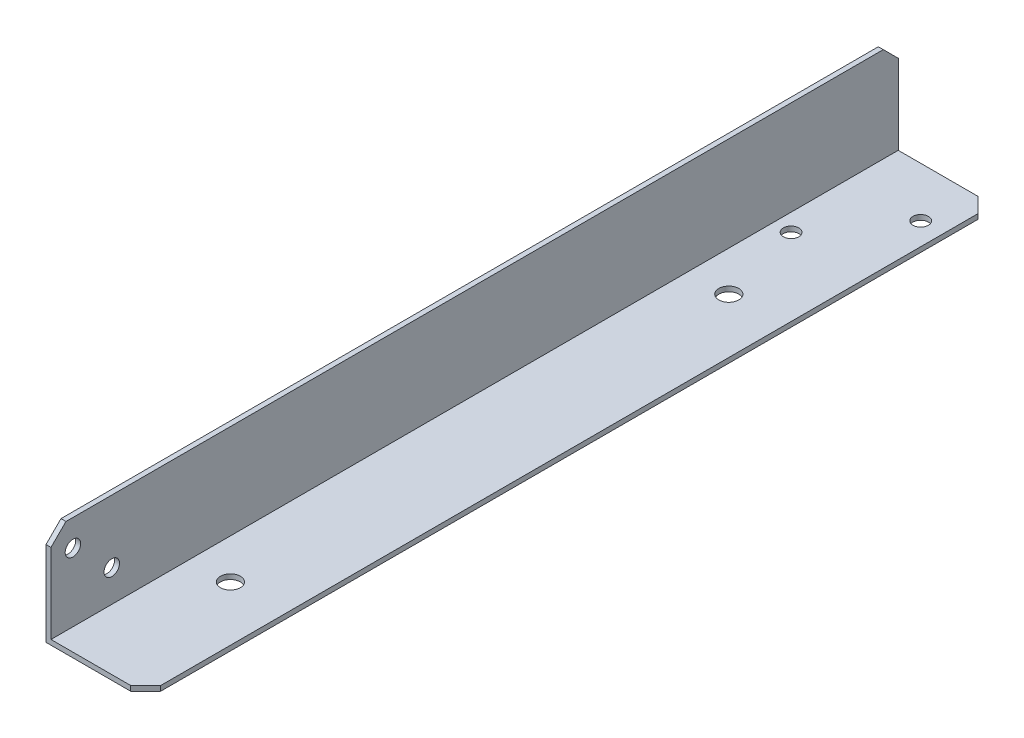
SolidWorks part; units mm, degrees
material "6063-T5"
ref_plane "Спереди" through (0, 0, 0) normal (0, 0, 1) x (1, 0, 0)
ref_plane "Сверху" through (0, 0, 0) normal (0, 1, 0) x (1, 0, 0)
ref_plane "Справа" through (0, 0, 0) normal (1, 0, 0) x (0, 0, -1)
sketch "Sketch1" plane through (0, 0, 0) normal (0, 0, 1) x (1, 0, 0)
  line L0 (0, 0) -> (20, 0)
  line L1 (20, 0) -> (20, 1)
  line L2 (20, 1) -> (1, 1)
  line L3 (1, 1) -> (1, 20)
  line L4 (1, 20) -> (0, 20)
  line L5 (0, 20) -> (0, 0)
  dimension "D1" = 20
  dimension "D2" = 20
  dimension "D3" = 1
  dimension "D4" = 1
extrude "Base" add sketch "Sketch1" along normal blind 170
chamfer "Chamfer1" distance 3 angle 45 4 edges at (20, 0.5, 170) (0.5, 20, 170) (0.5, 20, 0) (20, 0.5, 0)
sketch "Sketch4" plane through (2, 1, 0) normal (0, 1, 0) x (0, 0, -1)
  line L0 (-167, 2) -> (-3, 2) construction
  line L1 (0, -15) -> (0, 1) construction
  circle A0 centre (-10, -13.5) radius 1.55
  circle A1 centre (-25, -2.5) radius 1.55
  dimension "D5" = 3.1
  dimension "D6" = 3.1
  dimension "D1" = 4.5
  dimension "D2" = 15.5
  dimension "D3" = 10
  dimension "D4" = 25
extrude "CarriageSide" cut sketch "Sketch4" against normal through all
sketch "Sketch6" plane through (1, 0, 0) normal (1, 0, 0) x (0, 0, -1)
  line L1 (-170, 1) -> (-170, 17) construction
  line L2 (-170, 0) -> (0, 0) construction
  circle A0 centre (-165.6, 14.68) radius 1.55
  circle A1 centre (-157.8, 7.38) radius 1.55
  dimension "D5" = 3.1
  dimension "D1" = 7.8
  dimension "D2" = 7.38
  dimension "D3" = 7.3
  dimension "D4" = 4.4
hole_wizard "Ø4.0 (4) Cable tie Holes" positions "Sketch8" profile "Sketch9" hole size "Ø4.0" standard "ANSI Metric" end condition through all
sketch "Sketch8" plane through (0, 1, 0) normal (0, 1, 0) x (1, 0, 0)
  line L0 (0, -167) -> (0, -3) construction
  line L1 (17, 0) -> (1, 0) construction
  point P0 (9, -42)
  point P2 (9, -142)
  point P5 (0, 0)
  dimension "D1" = 9
  dimension "D2" = 42
  dimension "D3" = 142
sketch "Sketch9" plane through (9, 1, 42) normal (1, 0, 0) x (0, 0, 1)
  line L0 (0, 0) -> (0, 1)
  line L1 (0, 1) -> (2, 1)
  line L2 (2, 1) -> (2, 0)
  line L5 (2, 0) -> (0, 0)
  line L11 (0, -6.35) -> (0, 107.95) construction
  dimension "Thru Hole Dia." = 4
  dimension "Thru Hole Depth" = 1
hole_wizard "Ø3.1 (3.1) CableChainSideHoles" positions "Sketch10" profile "Sketch11" hole size "Ø3.1" standard "ANSI Metric" end condition through all
sketch "Sketch10" plane through (1, 0, 0) normal (1, 0, 0) x (0, 0, -1)
  line L0 (-167, 0) -> (-3, 0) construction
  line L1 (-170, 1) -> (-170, 17) construction
  point P0 (-165.6, 14.68)
  point P2 (-157.8, 7.38)
  dimension "D1" = 7.3
  dimension "D2" = 7.8
  dimension "D3" = 7.38
  dimension "D4" = 4.4
sketch "Sketch11" plane through (1, 14.68, 165.6) normal (0, 1, 0) x (0, 0, -1)
  line L0 (0, 0) -> (0, 1)
  line L1 (0, 1) -> (1.55, 1)
  line L2 (1.55, 1) -> (1.55, 0)
  line L5 (1.55, 0) -> (0, 0)
  line L11 (0, -6.35) -> (0, 107.95) construction
  dimension "Thru Hole Dia." = 3.1
  dimension "Thru Hole Depth" = 1
equation "\"D2@Sketch1\"=\"D1@Sketch1\""
equation "\"D4@Sketch1\"=\"D3@Sketch1\""
